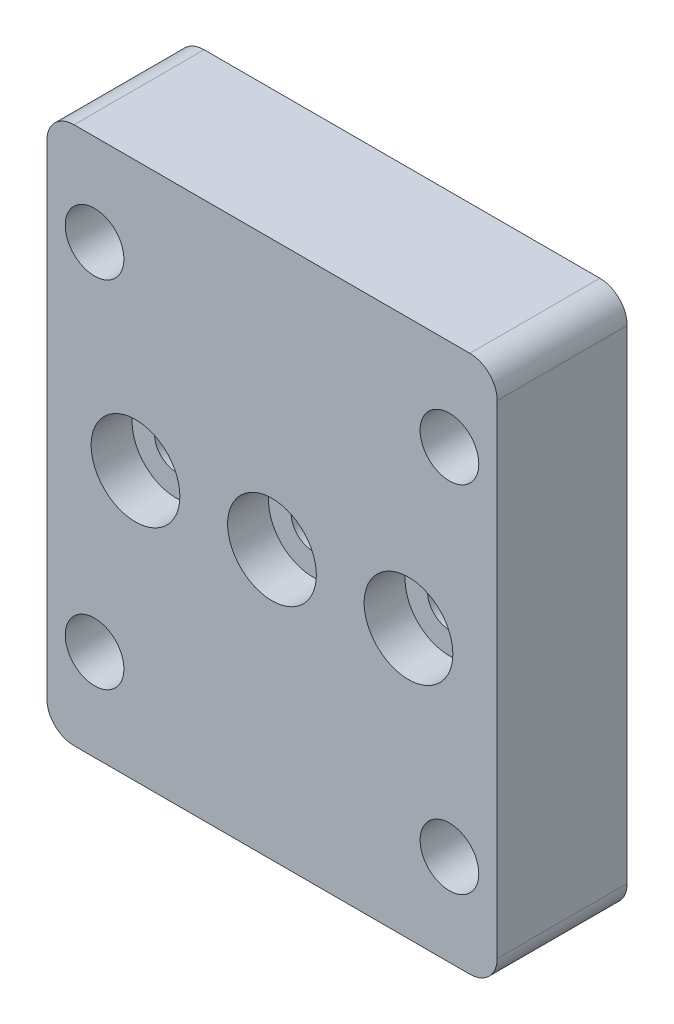
SolidWorks part; units mm, degrees
material "AISI 1045 Steel, cold drawn"
ref_plane "Front Plane" through (0, 0, 0) normal (0, 0, 1) x (1, 0, 0)
ref_plane "Top Plane" through (0, 0, 0) normal (0, 1, 0) x (1, 0, 0)
ref_plane "Right Plane" through (0, 0, 0) normal (1, 0, 0) x (0, 0, -1)
sketch "Sketch1" plane through (0, 0, 0) normal (0, 0, 1) x (1, 0, 0)
  line L0 (10, 0) -> (-10, 0) construction
  line L1 (13, -13) -> (-13, -13) construction
  line L2 (13, -13) -> (13, 13) construction
  line L3 (13, 13) -> (-13, 13) construction
  line L4 (-13, -13) -> (-13, 13) construction
  line L5 (13, -13) -> (-13, 13) construction
  line L6 (13, 13) -> (-13, -13) construction
  line L7 (16.5, -19.7) -> (-16.5, -19.7)
  line L8 (16.5, -19.7) -> (16.5, 19.7)
  line L9 (16.5, 19.7) -> (-16.5, 19.7)
  line L10 (-16.5, -19.7) -> (-16.5, 19.7)
  line L11 (16.5, -19.7) -> (-16.5, 19.7) construction
  line L12 (16.5, 19.7) -> (-16.5, -19.7) construction
  point P0 (0, 0)
  point P6 (0, 0)
  point P14 (0, 0)
  dimension "D1" = 26
  dimension "D2" = 20
  dimension "D3" = 33
  dimension "D4" = 39.4
extrude "Boss-Extrude1" add sketch "Sketch1" along normal blind 9.525
hole_wizard "CBORE for M3 SHCS1" positions "Sketch2" profile "Sketch3" counterbore size "M3" standard "ANSI Metric" end condition through all
sketch "Sketch2" plane through (0, 0, 9.525) normal (0, 0, 1) x (1, 0, 0)
  line L0 (13, 13) -> (-13, -13) construction
  point P0 (-10, 0)
  point P3 (0, 0)
  point P7 (10, 0)
sketch "Sketch3" plane through (-10, 0, 9.525) normal (1, 0, 0) x (0, -1, 0)
  line L0 (0, 0) -> (0, 9.525)
  line L1 (0, 9.525) -> (1.6, 9.525)
  line L3 (1.6, 9.525) -> (1.6, 3)
  line L4 (1.6, 3) -> (3.25, 3)
  line L5 (3.25, 3) -> (3.25, 0)
  line L7 (3.25, 0) -> (0, 0)
  line L11 (0, -6.35) -> (0, 107.95) construction
  dimension "Thru Hole Dia." = 3.2
  dimension "Thru Hole Depth" = 9.525
  dimension "C'Bore Dia." = 6.5
  dimension "C'Bore Depth" = 3
hole_wizard "M4 Clearance Hole1" positions "Sketch4" profile "Sketch5" hole size "M4" standard "ANSI Metric" end condition through all
sketch "Sketch4" plane through (0, 0, 9.525) normal (0, 0, 1) x (1, 0, 0)
  point P0 (-13, 13)
  point P3 (-13, -13)
  point P6 (13, -13)
  point P9 (13, 13)
sketch "Sketch5" plane through (-13, 13, 9.525) normal (1, 0, 0) x (0, -1, 0)
  line L0 (0, 0) -> (0, 9.525)
  line L1 (0, 9.525) -> (2.15, 9.525)
  line L2 (2.15, 9.525) -> (2.15, 0)
  line L5 (2.15, 0) -> (0, 0)
  line L11 (0, -6.35) -> (0, 107.95) construction
  dimension "Thru Hole Dia." = 4.3
  dimension "Thru Hole Depth" = 9.525
fillet "Fillet1" radius 2 4 edges at (16.5, 19.7, 4.7625) (16.5, -19.7, 4.7625) (-16.5, -19.7, 4.7625) (-16.5, 19.7, 4.7625)
